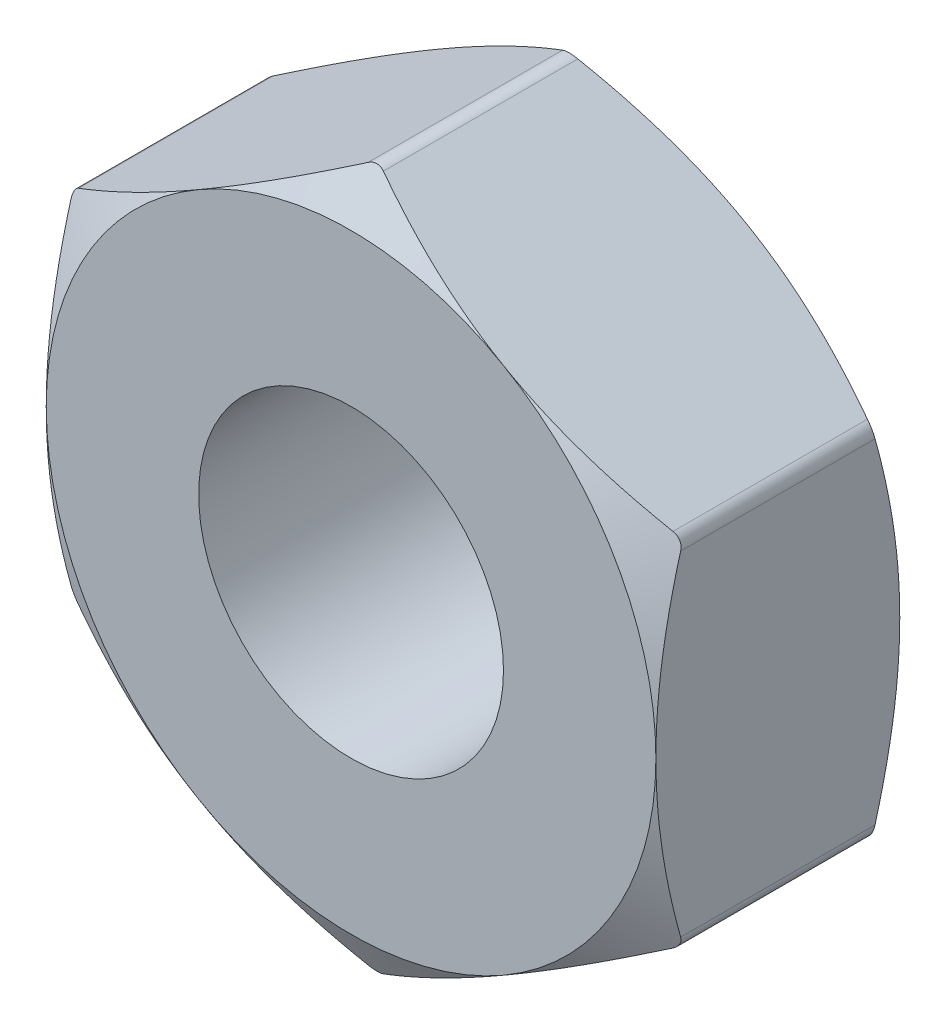
SolidWorks part; units mm, degrees
ref_plane "Front" through (0, 0, 0) normal (0, 0, 1) x (1, 0, 0)
ref_plane "Top" through (0, 0, 0) normal (0, 1, 0) x (1, 0, 0)
ref_plane "Right" through (0, 0, 0) normal (1, 0, 0) x (0, 0, -1)
sketch "Sketch1" plane through (0, 0, 0) normal (0, 0, 1) x (1, 0, 0)
  line L0 (0, 1) -> (0, 0.6) construction
  line L1 (-2, 1.1547) -> (-2, -1.1547)
  line L2 (-2, -1.1547) -> (0, -2.3094)
  line L3 (0, -2.3094) -> (2, -1.1547)
  line L4 (2, -1.1547) -> (2, 1.1547)
  line L5 (2, 1.1547) -> (0, 2.3094)
  line L6 (0, 2.3094) -> (-2, 1.1547)
  circle A0 centre (0, 0) radius 2 construction
  circle A1 centre (0, 0) radius 1 construction
  point P10 (0, 1)
  dimension "Width" = 4
  dimension "Thread Size" = 2
  dimension "Thread Pitch" = 0.4
sketch "Sketch2" plane through (0, 0, 0) normal (1, 0, 0) x (0, 0, -1)
  line L0 (-0.8, 0) -> (0.8, 0) construction
  line L1 (-0.8, 2.3094) -> (0.8, 2.3094) construction
  dimension "Height" = 1.6
sketch "Sketch15" plane through (0, 0, 0) normal (0, 0, 1) x (1, 0, 0)
  line L1 (0, 2.3094) -> (-2, 1.1547)
  line L2 (-2, 1.1547) -> (-2, -1.1547)
  line L3 (-2, -1.1547) -> (0, -2.3094)
  line L4 (0, -2.3094) -> (2, -1.1547)
  line L5 (2, -1.1547) -> (2, 1.1547)
  line L6 (2, 1.1547) -> (0, 2.3094)
  circle A0 centre (0, 0) radius 2 construction
extrude "Boss-Extrude2" add sketch "Sketch15" along normal mid plane 1.6
sketch "Sketch16" plane through (0, 0, 0) normal (0, 0, 1) x (1, 0, 0)
  circle A0 centre (0, 0) radius 1 construction
  circle A1 centre (0, 0) radius 1
sketch "Sketch4" [suppressed] plane through (0, 0, -0.8) normal (0, 0, -1) x (-1, 0, 0)
  circle A0 centre (0, 0) radius 1 construction
  circle A1 centre (0, 0) radius 1
extrude "Cut-Extrude4" cut sketch "Sketch16" against normal through all both and the other way through all
sketch "Sketch7" plane through (0, 0, 0.8) normal (0, 0, 1) x (1, 0, 0)
  circle A0 centre (0, 0) radius 2 construction
  circle A1 centre (0, 0) radius 2
extrude "Cut-Extrude5" cut sketch "Sketch7" against normal through all draft 60 flip side to cut
mirror "Mirror4" about plane through (0, 0, 0) normal (0, 0, 1) of "Cut-Extrude5"
fillet "Fillet2" radius 0.1 6 edges at (-2, 1.1547, 0) (-2, -1.1547, 0) (0, -2.3094, 0) (2, -1.1547, 0) (2, 1.1547, 0) (0, 2.3094, 0)
sketch "Sketch8" plane through (0, 0, 0.8) normal (0, 0, 1) x (1, 0, 0)
  line L0 (0.2588, -0.9659) -> (0, 0) construction
  line L2 (0, 1) -> (0, 0.6) construction
  circle A0 centre (0, 0) radius 1 construction
  point P0 (0.2588, -0.9659)
  dimension "D1" = 15
sketch "Sketch13" [suppressed] plane through (0, 0, -0.8) normal (0, 0, -1) x (-1, 0, 0)
  circle A0 centre (0, 0) radius 1 construction
  circle A1 centre (0, 0) radius 1
extrude "Boss-Extrude1" [suppressed] add sketch "Sketch13" against normal up to surface (1.6 mm away) separate body
curve "Helix/Spiral3" [suppressed] pitch 0.4 height 2.4 turns 6
sketch "Sketch12" [suppressed] plane through (0, 0, 0) normal (1, 0, 0) x (0, 0, -1)
  line L0 (1.15, 1) -> (0.8, 1)
  line L1 (1.15, 1) -> (1, 0.7402)
  line L2 (1, 0.7402) -> (0.95, 0.7402)
  line L3 (0.95, 0.7402) -> (0.8, 1)
  line L4 (0.975, 0.7402) -> (0.975, 1) construction
  line L5 (0.875, 0.8701) -> (1.075, 0.8701) construction
  dimension "D1" = 60
  dimension "D2" = 0.05
  dimension "D3" = 0.2
sweep "Cut-Sweep1" [suppressed] cut profiles "Sketch12" path "Helix/Spiral3"
sketch "Sketch17" [suppressed] plane through (0, 0, 0.8) normal (0, 0, 1) x (1, 0, 0)
  circle A1 centre (0, 0) radius 1
  circle A2 centre (0, 0) radius 1
  dimension "D1" = 0
extrude "Boss-Extrude3" [suppressed] add sketch "Sketch17" against normal up to surface (1.6 mm away)
combine bodies "Combine1" [suppressed] operation type subtract main body 127 bodies to subtract 118
sketch "Sketch10" [suppressed] plane through (0, 0, 0.8) normal (0, 0, 1) x (1, 0, 0)
  circle A0 centre (0, 0) radius 1 construction
  circle A1 centre (0, 0) radius 1 construction
  circle A2 centre (0, 0) radius 1.04
  dimension "D1" = 0.04
extrude "Cut-Extrude2" [suppressed] cut sketch "Sketch10" against normal through all draft 45
sketch "Sketch11" [suppressed] plane through (0, 0, -0.8) normal (0, 0, -1) x (-1, 0, 0)
  circle A1 centre (0, 0) radius 1.04 construction
  circle A2 centre (0, 0) radius 1.04
extrude "Cut-Extrude3" [suppressed] cut sketch "Sketch11" against normal through all draft 45
equation "\"D1\"= \"Height@Sketch2\""
equation "\"D3@Helix/Spiral3\"=\"Height@Sketch2\"+\"Thread Pitch@Sketch1\"*2"
equation "\"D4@Helix/Spiral3\"=\"Thread Pitch@Sketch1\""
equation "\"D2@Sketch12\" = \"D4@Helix/Spiral3\"*.125"
equation "\"D3@Sketch12\" = \"D4@Helix/Spiral3\"*.50"
equation "\"D1@Boss-Extrude2\"=\"Height@Sketch2\""
equation "\"D1@Fillet2\"=\"Width@Sketch1\"*0.025"
equation "\"D1@Sketch10\"=\"Thread Pitch@Sketch1\"*0.1"
